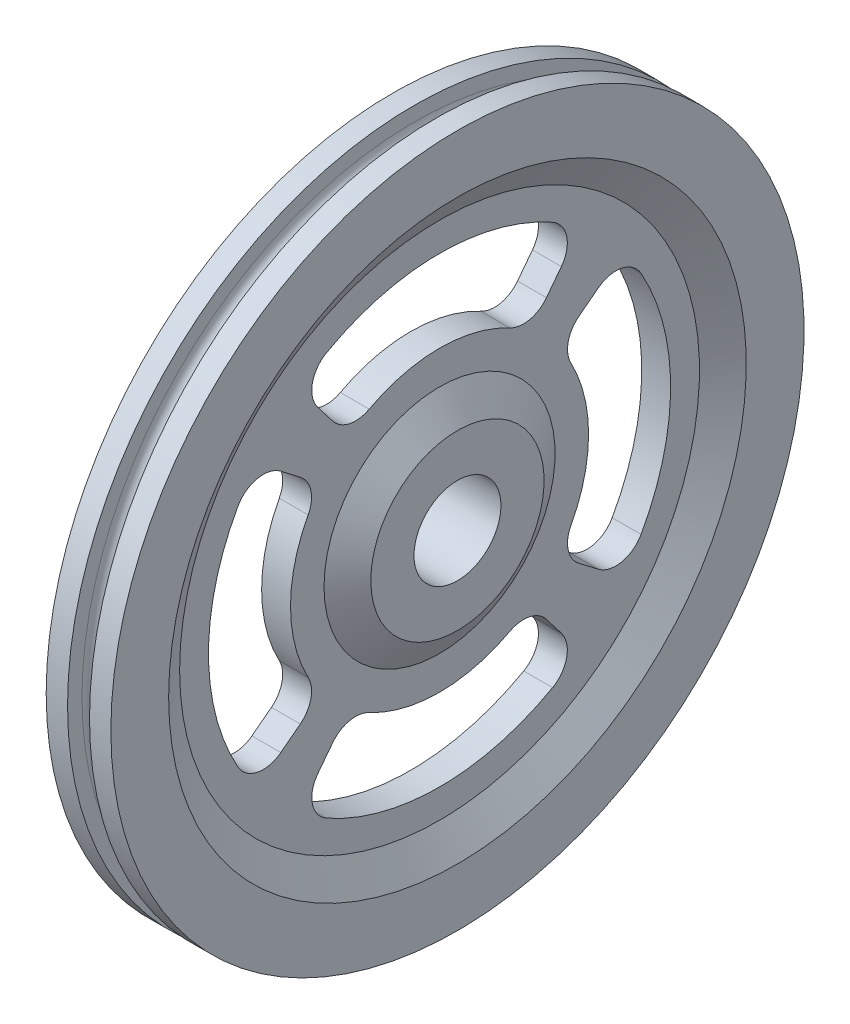
SolidWorks part; units mm, degrees
material "Plain Carbon Steel"
ref_plane "Front Plane" through (0, 0, 0) normal (0, 0, 1) x (1, 0, 0)
ref_plane "Top Plane" through (0, 0, 0) normal (0, 1, 0) x (1, 0, 0)
ref_plane "Right Plane" through (0, 0, 0) normal (1, 0, 0) x (0, 0, -1)
sketch "Sketch1" plane through (0, 0, 0) normal (0, 0, 1) x (1, 0, 0)
  line L3 (-7.112, 19.05) -> (-3.175, 25.4)
  line L4 (-3.175, 25.4) -> (-3.175, 57.15)
  line L5 (-3.175, 57.15) -> (-7.112, 63.5)
  line L6 (-7.112, 63.5) -> (-7.112, 76.2)
  line L7 (-7.112, 76.2) -> (-2.413, 76.2)
  line L8 (7.112, 76.2) -> (7.112, 63.5)
  line L9 (7.112, 63.5) -> (3.175, 57.15)
  line L10 (3.175, 57.15) -> (3.175, 25.4)
  line L11 (3.175, 25.4) -> (7.112, 19.05)
  line L16 (-7.112, 19.05) -> (-7.112, 9.5567)
  line L17 (-7.112, 9.5567) -> (7.112, 9.5567)
  line L18 (7.112, 9.5567) -> (7.112, 19.05)
  line L19 (-2.413, 73.025) -> (-2.413, 76.2)
  line L20 (2.413, 73.025) -> (2.413, 76.2)
  line L21 (2.413, 76.2) -> (7.112, 76.2)
  line L22 (0, 0) -> (7.112, 0) construction
  arc A0 (-2.413, 73.025) -> (2.413, 73.025) centre (0, 73.025) ccw
  point P1 (0, 9.5567)
  dimension "D11" = 4.826
  dimension "D1" = 14.224
  dimension "D2" = 9.5567
  dimension "D3" = 19.05
  dimension "D4" = 25.4
  dimension "D5" = 57.15
  dimension "D6" = 63.5
  dimension "D7" = 76.2
  dimension "D8" = 6.35
  dimension "D9" = 3.175
  dimension "D10" = 14.224
  dimension "D12" = 73.025
revolve "Revolve1" add sketch "Sketch1" angle 360 about L22
sketch "Sketch2" plane through (3.175, 0, 0) normal (1, 0, 0) x (0, 0, -1)
  line L0 (0, 32.766) -> (0, 50.8) construction
  line L1 (23.4964, 30.6212) -> (26.7819, 34.9029)
  line L2 (-23.4964, 30.6212) -> (-26.7819, 34.9029)
  arc A0 (24.8504, 44.3068) -> (-24.8504, 44.3068) centre (0, 0) ccw
  arc A1 (15.4621, 28.8883) -> (-15.4621, 28.8883) centre (0, 0) ccw
  arc A2 (26.7819, 34.9029) -> (24.8504, 44.3068) centre (21.7441, 38.7685) ccw
  arc A3 (15.4621, 28.8883) -> (23.4964, 30.6212) centre (18.4587, 34.4868) ccw
  arc A4 (-15.4621, 28.8883) -> (-23.4964, 30.6212) centre (-18.4587, 34.4868) cw
  arc A5 (-26.7819, 34.9029) -> (-24.8504, 44.3068) centre (-21.7441, 38.7685) cw
  dimension "D1" = 101.6
  dimension "D2" = 65.532
  dimension "D5" = 6.35
  dimension "D3" = 37.5
  dimension "D4" = 75
extrude "Cut-Extrude1" cut sketch "Sketch2" against normal up to next
pattern_circular "CirPattern1" count 4 over 360 about axis through (0, 0, 0) along (-1, 0, 0) of "Cut-Extrude1" reverse direction yes
